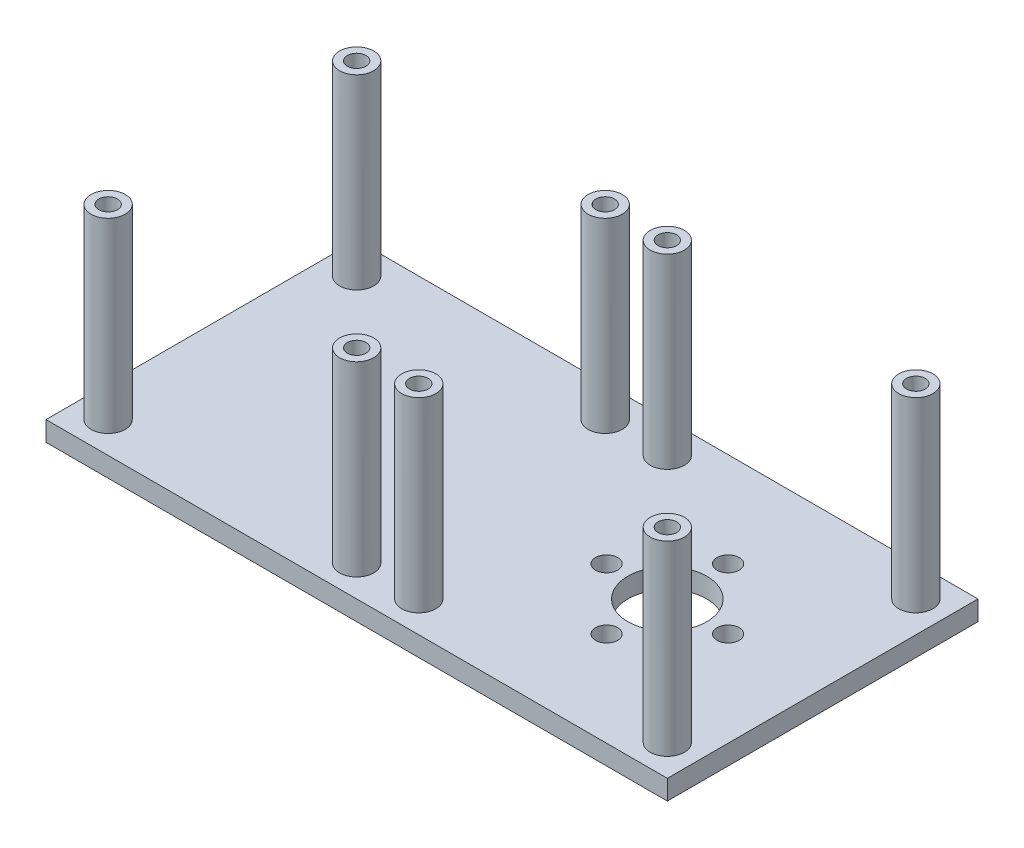
SolidWorks part; units mm, degrees
material "Copper"
ref_plane "Front Plane" through (0, 0, 0) normal (0, 0, 1) x (1, 0, 0)
ref_plane "Top Plane" through (0, 0, 0) normal (0, 1, 0) x (1, 0, 0)
ref_plane "Right Plane" through (0, 0, 0) normal (1, 0, 0) x (0, 0, -1)
sketch "Sketch1" plane through (0, 0, 0) normal (0, 1, 0) x (1, 0, 0)
  line L1 (-25, -25) -> (25, -25)
  line L2 (-25, -25) -> (-25, 25)
  line L3 (-25, 25) -> (25, 25)
  line L4 (25, -25) -> (25, 25)
  line L5 (-25, -25) -> (25, 25) construction
  line L6 (-25, 25) -> (25, -25) construction
  circle A0 centre (0, 0) radius 6.35
  circle A1 centre (-9.779, 0) radius 1.778
  circle A2 centre (9.779, 0) radius 1.778
  circle A3 centre (0, 9.779) radius 1.778
  circle A4 centre (0, -9.779) radius 1.778
  point P0 (0, 0)
  dimension "D3" = 12.7
  dimension "D8" = 3.556
  dimension "D9" = 3.556
  dimension "D10" = 3.556
  dimension "D11" = 3.556
  dimension "D1" = 50
  dimension "D2" = 50
  dimension "D4" = 9.779
  dimension "D5" = 9.779
  dimension "D6" = 9.779
  dimension "D7" = 9.779
extrude "Boss-Extrude1" add sketch "Sketch1" along normal blind 3.175
sketch "Sketch2" plane through (0, 3.175, 0) normal (0, 1, 0) x (1, 0, 0)
  line L0 (25, 25) -> (-25, 25) construction
  line L1 (-25, 25) -> (-25, -25) construction
  line L2 (25, -25) -> (25, 25) construction
  line L3 (-25, -25) -> (25, -25) construction
  circle A0 centre (20, -20) radius 2.75
  circle A1 centre (-20, -20) radius 2.75
  circle A2 centre (-20, 20) radius 2.75
  circle A3 centre (20, 20) radius 2.75
  circle A4 centre (-20, -20) radius 1.5
  circle A5 centre (20, -20) radius 1.5
  circle A6 centre (-20, 20) radius 1.5
  circle A7 centre (20, 20) radius 1.5
  dimension "D1" = 5
  dimension "D9" = 3
  dimension "D10" = 5.5
  dimension "D11" = 3
  dimension "D12" = 5.5
  dimension "D13" = 3
  dimension "D14" = 5.5
  dimension "D15" = 3
  dimension "D16" = 5.5
  dimension "D2" = 5
  dimension "D3" = 5
  dimension "D4" = 5
  dimension "D5" = 5
  dimension "D6" = 5
  dimension "D7" = 5
  dimension "D8" = 5
extrude "Boss-Extrude2" add sketch "Sketch2" along normal blind 30
sketch "Sketch3" plane through (0, 0, 0) normal (0, 1, 0) x (1, 0, 0)
  line L1 (-25, 25) -> (-75, 25)
  line L2 (-25, 25) -> (-25, -25)
  line L3 (-25, -25) -> (-75, -25)
  line L4 (-75, 25) -> (-75, -25)
  dimension "D1" = 50
  dimension "D2" = 50
extrude "Boss-Extrude3" add sketch "Sketch3" along normal up to surface (3.175 mm away) up to face at (20, 3.175, -22.75)
sketch "Sketch4" plane through (0, 3.175, 0) normal (0, 1, 0) x (1, 0, 0)
  line L0 (-75, -25) -> (-75, 25) construction
  line L1 (25, 25) -> (-75, 25) construction
  line L2 (-75, -25) -> (25, -25) construction
  circle A0 centre (-70, 20) radius 2.75
  circle A1 centre (-30, 20) radius 1.5
  circle A2 centre (-70, -20) radius 2.75
  circle A3 centre (-30, -20) radius 2.75
  circle A4 centre (-30, -20) radius 1.5
  circle A5 centre (-70, -20) radius 1.5
  circle A6 centre (-70, 20) radius 1.5
  circle A7 centre (-30, 20) radius 2.75
  circle A8 centre (-20, 20) radius 2.75 construction
  circle A9 centre (-20, -20) radius 1.5 construction
  dimension "D6" = 3
  dimension "D7" = 5.5
  dimension "D8" = 3
  dimension "D9" = 5.5
  dimension "D12" = 3
  dimension "D13" = 5.5
  dimension "D14" = 5.5
  dimension "D15" = 3
  dimension "D1" = 5
  dimension "D2" = 5
  dimension "D3" = 5
  dimension "D4" = 10
  dimension "D5" = 10
  dimension "D10" = 5
  dimension "D11" = 5
  dimension "D16" = 5
extrude "Boss-Extrude4" add sketch "Sketch4" along normal blind 30
